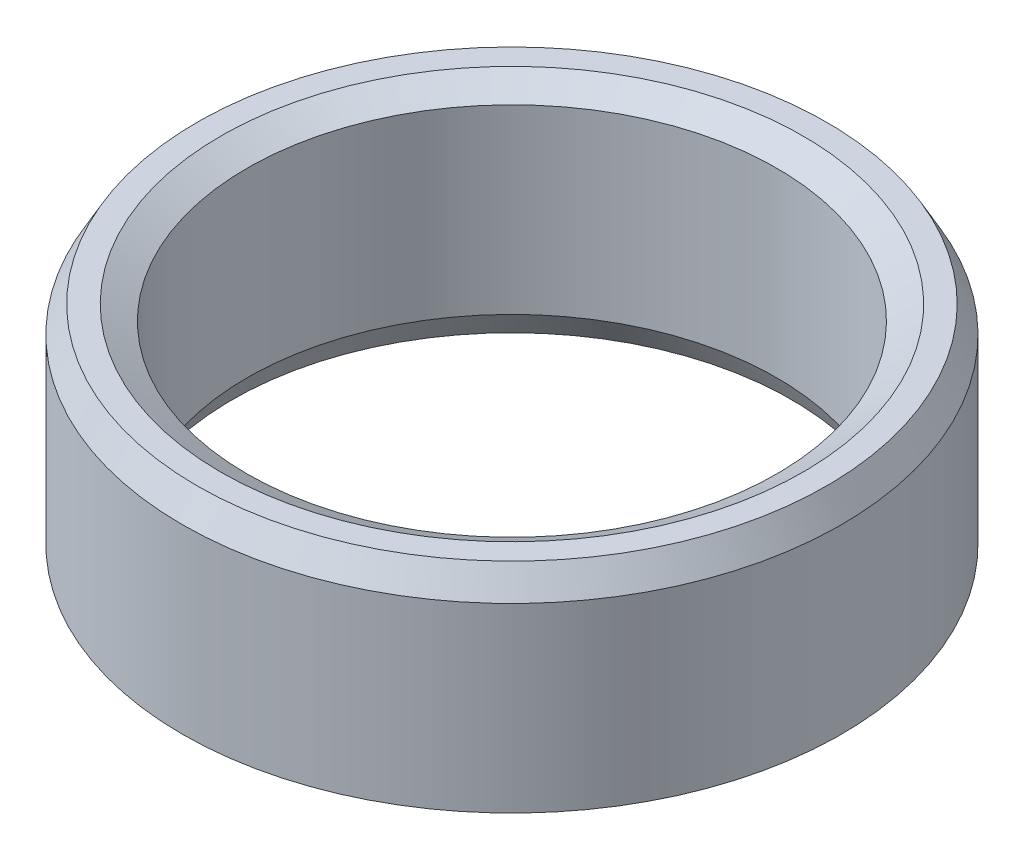
SolidWorks part; units mm, degrees
ref_plane "Front Plane" through (0, 0, 0) normal (0, 0, 1) x (1, 0, 0)
ref_plane "Top Plane" through (0, 0, 0) normal (0, 1, 0) x (1, 0, 0)
ref_plane "Right Plane" through (0, 0, 0) normal (1, 0, 0) x (0, 0, -1)
sketch "Sketch1" plane through (0, 0, 0) normal (0, 1, 0) x (1, 0, 0)
  circle A0 centre (0, 0) radius 50
  dimension "SLEEVE_OD" = 100
extrude "Boss-Extrude1" add sketch "Sketch1" along normal blind 33.7568
sketch "Sketch2" plane through (0, 0, 0) normal (0, 1, 0) x (1, 0, 0)
  circle A0 centre (0, 0) radius 40.1804
  dimension "BORE_D" = 80.3609
extrude "Cut-Extrude1" cut sketch "Sketch2" along normal through all
chamfer "Chamfer1" distance 3.9882 angle 29.219 4 edges at (0, 33.7568, 40.1804) (0, 0, 40.1804) (0, 0, 50) (0, 33.7568, 50) first distance on face at (0, 33.7568, 40.1804) first distance on face at (0, 0, 40.1804) first distance on face at (0, 33.7568, 50)
